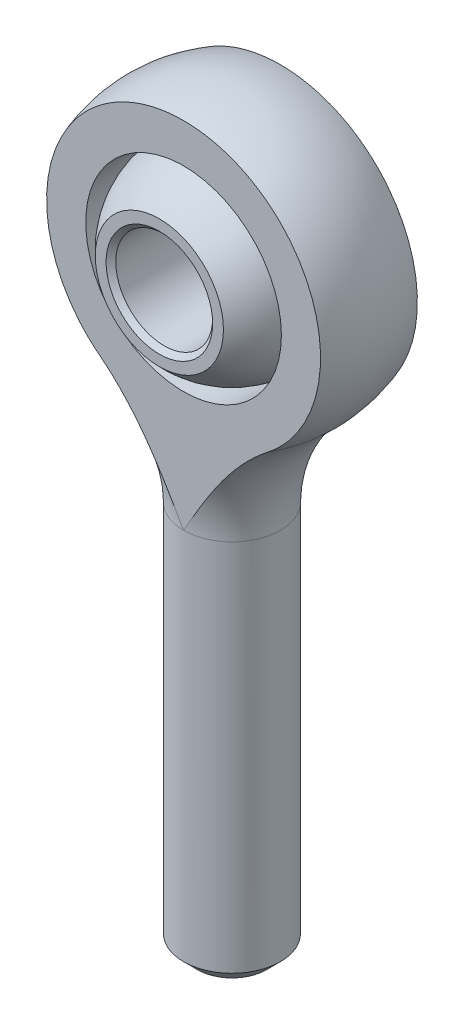
SolidWorks part; units mm, degrees
ref_plane "Front" through (0, 0, 0) normal (0, 0, 1) x (1, 0, 0)
ref_plane "Top" through (0, 0, 0) normal (0, 1, 0) x (1, 0, 0)
ref_plane "Right" through (0, 0, 0) normal (1, 0, 0) x (0, 0, -1)
sketch "Sketch1" plane through (0, 0, 0) normal (0, 0, 1) x (1, 0, 0)
  line L0 (0, 0) -> (0, -25.4)
  line L1 (0, -25.4) -> (3.175, -25.4)
  line L2 (3.175, -25.4) -> (3.175, 0)
  line L3 (3.175, 0) -> (0, 0)
  line L5 (0, 23.8125) -> (0, 0) construction
  line L6 (0, 23.8125) -> (9.525, 23.8125) construction
  line L7 (9.525, 23.8125) -> (9.525, 14.2875) construction
  line L8 (-3.175, -25.4) -> (-3.175, 0) construction
  arc A0 (6.3827, 7.2174) -> (0, 23.8125) centre (0, 14.2875) ccw construction
  circle A1 centre (0, 14.2875) radius 3.175 construction
  circle A2 centre (0, 14.2875) radius 6.35 construction
  circle A3 centre (0, 14.2875) radius 6.4135 construction
  arc A4 (3.175, 0) -> (6.3827, 7.2174) centre (12.8984, 0) cw construction
  dimension "A" = 6.35
  dimension "Ball Dia" = 12.7
  dimension "B" = 19.05
  dimension "D1" = 12.827
  dimension "D" = 39.6875
  dimension "E" = 25.4
  dimension "Thread Dia" = 6.35
revolve "Revolve1" add sketch "Sketch1" angle 360 about L5
chamfer "Chamfer2" distance 0.9068 angle 45 1 edges at (-3.175, -25.4, 0)
sketch "Sketch12" plane through (0, -25.4, 0) normal (0, -1, 0) x (1, 0, 0)
  circle A1 centre (0, 0) radius 2.2682
  circle A2 centre (0, 0) radius 2.2682
  dimension "D1" = 0
curve "Helix/Spiral1" pitch 0.9068 height 30.48 turns 33.6134
sketch "Sketch13" plane through (0, 0, 0) normal (0, 0, 1) x (1, 0, 0)
  line L0 (3.175, -25.4) -> (3.175, -26.1934)
  line L1 (3.175, -26.1934) -> (2.586, -25.8534)
  line L2 (2.586, -25.8534) -> (2.586, -25.74)
  line L3 (2.586, -25.74) -> (3.175, -25.4)
  line L4 (2.8805, -25.57) -> (2.8805, -26.0234) construction
  dimension "D1" = 60
  dimension "D3" = 0.4534
sweep "Cut-Sweep2" [suppressed] cut profiles "Sketch13" path "Helix/Spiral1"
sketch "Sketch4" plane through (0, 0, 0) normal (0, 0, 1) x (1, 0, 0)
  line L0 (3.175, 0) -> (0, 0) construction
  line L2 (0, 23.8125) -> (0, 0) construction
  line L3 (3.175, 0) -> (0, 0)
  line L5 (0, 23.8125) -> (0, 0)
  line L6 (0, 23.8125) -> (0, 26.3525) construction
  arc A0 (6.3827, 7.2174) -> (0, 23.8125) centre (0, 14.2875) ccw construction
  arc A1 (6.3827, 7.2174) -> (0, 23.8125) centre (0, 14.2875) ccw
  arc A2 (6.3827, 7.2174) -> (3.175, 0) centre (12.8984, 0) ccw construction
  arc A3 (6.3827, 7.2174) -> (3.175, 0) centre (12.8984, 0) ccw
  dimension "D1" = 2.54
revolve "Revolve2" add sketch "Sketch4" angle 360 about L6
sketch "Sketch5" plane through (0, 0, 0) normal (1, 0, 0) x (0, 0, -1)
  line L0 (3.175, 23.8125) -> (9.525, 23.8125)
  line L1 (-3.175, 23.8125) -> (3.175, 23.8125) construction
  line L2 (-3.175, 23.8125) -> (-3.175, 1.27)
  line L3 (-3.175, 0) -> (3.175, 0) construction
  line L4 (3.175, 23.8125) -> (3.175, 1.27)
  line L5 (9.525, 23.8125) -> (9.525, 0)
  line L6 (9.525, 0) -> (3.175, 0)
  line L7 (-3.175, 0) -> (-9.525, 0)
  line L8 (-9.525, 0) -> (-9.525, 23.8125)
  line L9 (-9.525, 23.8125) -> (-3.175, 23.8125)
  line L10 (3.175, 0) -> (3.175, 1.27)
  line L11 (-3.175, 0) -> (-3.175, 1.27)
  line L12 (-3.175, 1.27) -> (3.175, 1.27) construction
  line L13 (0, 0) -> (0, 1.27) construction
  arc A0 (6.3827, 7.2174) -> (-6.3827, 7.2174) centre (0, 14.2875) ccw construction
  dimension "F" = 6.35
  dimension "D2" = 1.27
  dimension "D1" = 6.35
extrude "Cut-Extrude1" cut sketch "Sketch5" against normal through all and the other way through all
sketch "Sketch6" plane through (0, 0, 0) normal (0, 0, 1) x (1, 0, 0)
  circle A0 centre (0, 14.2875) radius 6.4135 construction
  circle A1 centre (0, 14.2875) radius 6.4135
extrude "Cut-Extrude2" cut sketch "Sketch6" against normal through all and the other way through all
sketch "Sketch7" plane through (0, 0, 0) normal (0, 0, 1) x (1, 0, 0)
  line L0 (0, 20.6375) -> (0, 7.9375)
  line L1 (0, 23.8125) -> (0, 0) construction
  line L2 (0, 0) -> (0, 7.9375) construction
  arc A0 (0, 7.9375) -> (0, 20.6375) centre (0, 14.2875) ccw
  circle A1 centre (0, 14.2875) radius 6.35 construction
revolve "Revolve3" add sketch "Sketch7" angle 360 about L2
sketch "Sketch8" plane through (0, 0, 0) normal (1, 0, 0) x (0, 0, -1)
  line L0 (-3.175, 23.8125) -> (3.175, 23.8125) construction
  line L1 (-4.7625, 23.8125) -> (4.7625, 23.8125) construction
  line L2 (-4.7625, 23.8125) -> (-4.7625, 0)
  line L3 (-4.7625, 0) -> (4.7625, 0) construction
  line L4 (4.7625, 23.8125) -> (4.7625, 0)
  line L5 (4.7625, 23.8125) -> (9.525, 23.8125)
  line L6 (9.525, 23.8125) -> (9.525, 0)
  line L7 (9.525, 0) -> (4.7625, 0)
  line L8 (-4.7625, 0) -> (-9.525, 0)
  line L9 (-9.525, 0) -> (-9.525, 23.8125)
  line L10 (-9.525, 23.8125) -> (-4.7625, 23.8125)
  dimension "C" = 9.525
extrude "Cut-Extrude3" cut sketch "Sketch8" against normal through all and the other way through all
sketch "Sketch10" plane through (0, 0, 0) normal (0, 0, 1) x (1, 0, 0)
  circle A0 centre (0, 14.2875) radius 3.175 construction
  circle A1 centre (0, 14.2875) radius 3.175
extrude "Cut-Extrude4" cut sketch "Sketch10" against normal through all and the other way through all
chamfer "Chamfer1" distance 0.3175 angle 45 2 edges at (3.175, 14.2875, -4.7625) (3.175, 14.2875, 4.7625)
sketch "Sketch14" [suppressed] plane through (0, 0, 0) normal (1, 0, 0) x (0, 0, -1)
  line L0 (2.4016, 13.0969) -> (-2.4016, 13.0969) construction
  line L1 (3.9688, 13.0969) -> (-3.9688, 13.0969)
  line L2 (-3.9688, 13.0969) -> (-3.9688, 13.6049)
  line L3 (-2.6, 13.5616) -> (2.6, 13.5616)
  line L4 (-2.6, 13.5616) -> (-2.6, 8.6634) construction
  line L5 (3.9688, 13.6049) -> (3.9688, 13.0969)
  arc A0 (-3.9688, 13.6049) -> (-2.6, 13.5616) centre (-3.9688, -8.0834) cw
  arc A1 (2.6, 13.5616) -> (3.9688, 13.6049) centre (3.9688, -8.0834) cw
  point P11 (0, 13.0969)
  dimension "D1" = 7.9375
  dimension "D2" = 0.508
revolve "Revolve4" [suppressed] add sketch "Sketch14" angle 360
fillet "Fillet1" [suppressed] radius 0.508
sketch "Sketch11" plane through (0, 0, 0) normal (1, 0, 0) x (0, 0, -1)
  line L0 (0, 14.2875) -> (-4.7625, 15.4309) construction
  line L1 (3.175, 14.2875) -> (-3.175, 14.2875) construction
  line L2 (0, 14.2875) -> (-4.7625, 13.1441) construction
  line L3 (0, 23.8125) -> (0, 0) construction
  line L4 (-4.7625, 23.8125) -> (-4.7625, 0) construction
  line L5 (0, 14.2875) -> (0.0074, 14.2875) construction
  dimension "Swivel" = 27
sketch "Sketch15" plane through (0, 0, 0) normal (1, 0, 0) x (0, 0, -1)
  line L0 (-4.445, 11.1125) -> (4.445, 11.1125) construction
  line L1 (4.445, 17.4625) -> (-4.445, 17.4625) construction
  line L2 (-4.445, 11.1125) -> (4.445, 11.1125) construction
  line L3 (4.445, 17.4625) -> (-4.445, 17.4625) construction
  line L4 (-3.175, 23.2678) -> (-3.175, 7.2174) construction
  line L5 (3.175, 7.2174) -> (3.175, 23.2678) construction
  arc A0 (-4.7625, 10.0874) -> (4.7625, 10.0874) centre (0, 14.2875) ccw construction
  arc A1 (4.7625, 18.4876) -> (-4.7625, 18.4876) centre (0, 14.2875) ccw construction
  arc A2 (-3.175, 8.7882) -> (3.175, 8.7882) centre (0, 14.2875) ccw construction
  arc A3 (3.175, 19.7868) -> (-3.175, 19.7868) centre (0, 14.2875) ccw construction
equation "\"D1@Sketch1\"=\"Ball Dia@Sketch1\"*1.01"
equation "\"D1@Chamfer1\"=\"A@Sketch1\"/20"
equation "\"D1@Sketch5\"=\"Thread Dia@Sketch1\""
equation "\"D2@Sketch5\"=\"F@Sketch5\"/5"
equation "\"D3@Helix/Spiral1\" = \"E@Sketch1\" + .2"
equation "\"D2@Sketch13\" = \"D4@Helix/Spiral1\" * .125"
equation "\"D3@Sketch13\" = \"D4@Helix/Spiral1\" * .5"
equation "\"D1@Chamfer2\" = \"D4@Helix/Spiral1\" * 1"
